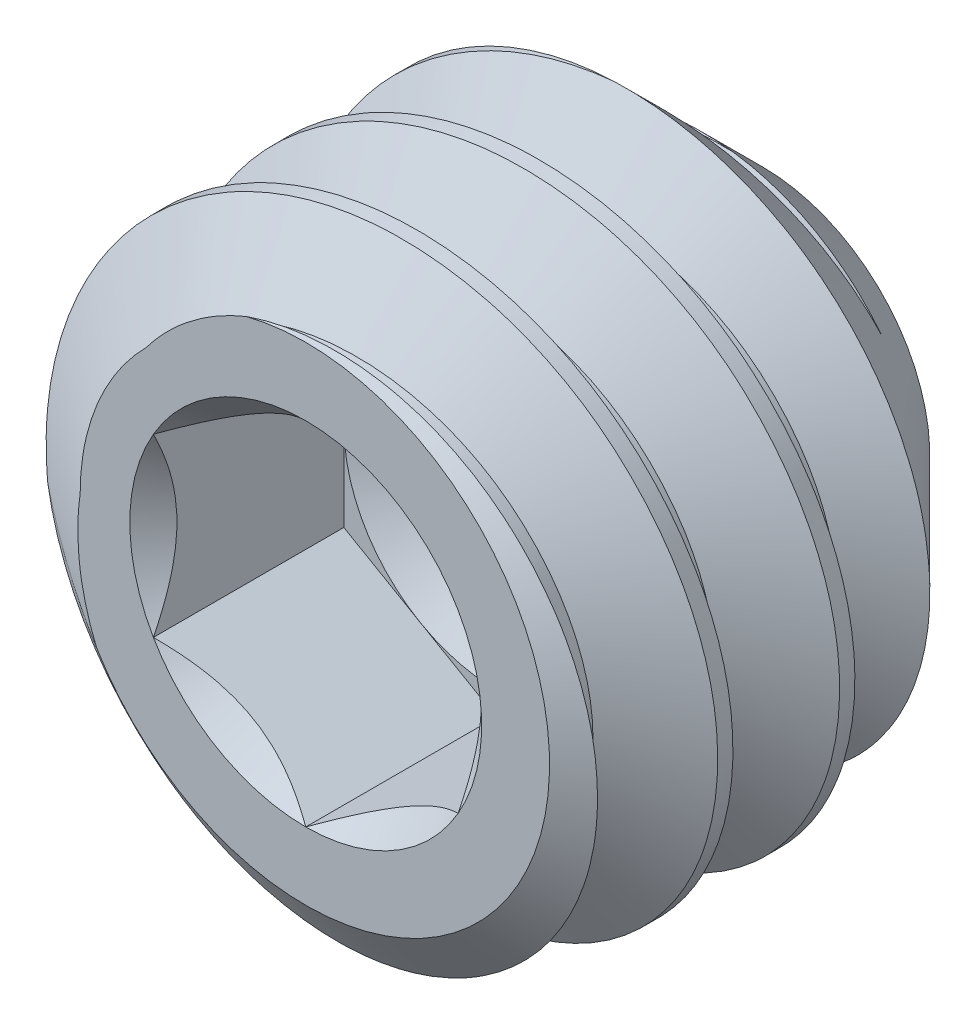
SolidWorks part; units mm, degrees
material "Plain Carbon Steel"
ref_plane "Front" through (0, 0, 0) normal (0, 0, 1) x (1, 0, 0)
ref_plane "Top" through (0, 0, 0) normal (0, 1, 0) x (1, 0, 0)
ref_plane "Right" through (0, 0, 0) normal (1, 0, 0) x (0, 0, -1)
sketch "Sketch22" plane through (0, 0, 0) normal (1, 0, 0) x (0, 0, -1)
  line L0 (-1.8586, 0) -> (-1.8586, 2.54)
  line L1 (-1.8586, 2.54) -> (-1.4139, 3.175)
  line L2 (-1.4139, 3.175) -> (1.4687, 3.175)
  line L3 (1.4687, 3.175) -> (2.9039, 1.7398)
  line L4 (2.9039, 1.7398) -> (1.8586, 0)
  line L5 (1.8586, 0) -> (-1.8586, 0)
  line L6 (1.8586, 0) -> (2.9039, 0) construction
  line L7 (2.9039, 0) -> (2.9039, 1.7398) construction
  line L8 (2.9039, -1.7398) -> (1.8586, 0) construction
  line L9 (-1.4139, -3.175) -> (1.4687, -3.175) construction
  dimension "Dia" = 6.35
  dimension "Length" = 4.7625
  dimension "D3" = 35
  dimension "D5" = 118
  dimension "D6" = 45
  dimension "D7" = 5.08
revolve "Revolve1" add sketch "Sketch22" angle 360 about L6
ref_plane "Plane1" through (0, 0, -2.9039) normal (0, 0, 1) x (1, 0, 0)
sketch "Sketch27" plane through (0, 0, -2.9039) normal (0, 0, 1) x (1, 0, 0)
  circle A0 centre (0, 0) radius 3.175 construction
  circle A1 centre (0, 0) radius 3.175
curve "Helix/Spiral1" pitch 1.27 height 6.0325 radius 3.175 centre (0, 0, -2.9039) axis (0, 0, 1) start towards (0, 1, 0)
sketch "Sketch28" plane through (0, 0, 0) normal (1, 0, 0) x (0, 0, -1)
  line L0 (2.9039, 3.175) -> (4.0152, 3.175)
  line L1 (4.0152, 3.175) -> (3.5389, 2.3501)
  line L2 (3.5389, 2.3501) -> (3.3802, 2.3501)
  line L3 (3.3802, 2.3501) -> (2.9039, 3.175)
  line L4 (3.1421, 2.7626) -> (3.7771, 2.7626) construction
  line L6 (-1.4139, 3.175) -> (1.4687, 3.175) construction
  line L7 (2.9039, 3.4925) -> (2.9039, -3.4925) construction
  dimension "D1" = 0.1588
  dimension "D3" = 60
  dimension "D2" = 0.635
sweep "Cut-Sweep2" cut profiles "Sketch28" path "Helix/Spiral1" align with end faces yes
sketch "Sketch23" plane through (0, 0, 1.8586) normal (0, 0, 1) x (1, 0, 0)
  line L1 (0, 1.8331) -> (-1.5875, 0.9165)
  line L2 (-1.5875, 0.9165) -> (-1.5875, -0.9165)
  line L3 (-1.5875, -0.9165) -> (0, -1.8331)
  line L4 (0, -1.8331) -> (1.5875, -0.9165)
  line L5 (1.5875, -0.9165) -> (1.5875, 0.9165)
  line L6 (1.5875, 0.9165) -> (0, 1.8331)
  circle A0 centre (0, 0) radius 1.5875 construction
  dimension "Hex" = 3.175
extrude "Cut-Extrude10" cut sketch "Sketch23" against normal blind 1.9844
sketch "Sketch24" plane through (0, 0, 1.8586) normal (0, 0, 1) x (1, 0, 0)
  circle A0 centre (0, 0) radius 1.8331
extrude "Cut-Extrude11" cut sketch "Sketch24" against normal through all draft 45
sketch "Sketch26" plane through (0, 0, -0.1258) normal (0, 0, 1) x (1, 0, 0)
  circle A0 centre (0, 0) radius 1.5875 construction
  circle A1 centre (0, 0) radius 1.5875
extrude "Cut-Extrude12" cut sketch "Sketch26" against normal through all draft 60
sketch "Sketch30" plane through (0, 0, 0) normal (1, 0, 0) x (0, 0, -1)
  line L0 (-1.4139, 3.175) -> (1.4687, 3.175) construction
  line L1 (-1.8586, 0) -> (-1.8586, 2.54) construction
  line L2 (2.9039, 0) -> (2.9039, 1.7398) construction
  line L3 (-1.4139, -3.175) -> (1.4687, -3.175) construction
  point P0 (-1.8586, 3.175)
  point P1 (2.9039, 3.175)
  point P2 (2.9039, -3.175)
  point P11 (-0.2711, -3.175)
  dimension "D1" = 3.175
sketch "Sketch31" plane through (0, 0, 0) normal (1, 0, 0) x (0, 0, -1)
  line L2 (1.8586, 0) -> (2.9039, -1.7398)
  line L3 (2.9039, 1.7398) -> (1.8586, 0)
equation "\"D7@Sketch22\"=\"Dia@Sketch22\"*.8"
equation "\"D1@Sketch28\" = \"D4@Helix/Spiral1\" * .125"
equation "\"D3@Helix/Spiral1\" = \"Length@Sketch22\" + \"D4@Helix/Spiral1\""
equation "\"D1@Sketch30\" = \"D4@Helix/Spiral1\" * 2.5"
equation "\"hex Depth@Cut-Extrude10\" = \"Hex@Sketch23\" * .625"
equation "\"D2@Sketch28\" = \"D4@Helix/Spiral1\" * .5"
